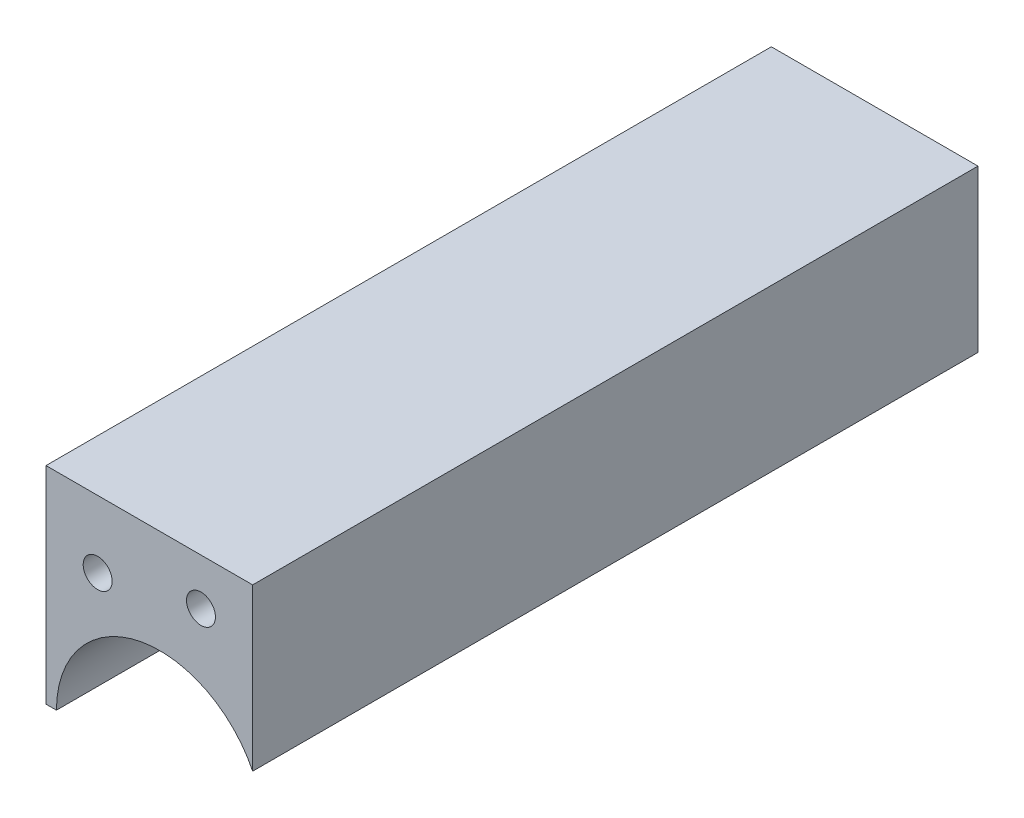
SolidWorks part; units mm, degrees
ref_plane "Front Plane" through (0, 0, 0) normal (0, 0, 1) x (1, 0, 0)
ref_plane "Top Plane" through (0, 0, 0) normal (0, 1, 0) x (1, 0, 0)
ref_plane "Right Plane" through (0, 0, 0) normal (1, 0, 0) x (0, 0, -1)
sketch "Sketch1" plane through (0, 0, 0) normal (0, 0, 1) x (1, 0, 0)
  line L1 (0, 0) -> (1.01, 0)
  line L2 (0, 0) -> (0, 20)
  line L3 (0, 20) -> (20, 20)
  line L4 (20, 4.3795) -> (20, 20)
  arc A0 (20, 4.3795) -> (1.01, 0) centre (11.01, 0) ccw
  circle A3 centre (5, 13.5) radius 1.4
  circle A4 centre (15, 15.5) radius 1.4
extrude "Boss-Extrude1" add sketch "Sketch1" along normal blind 70.2
